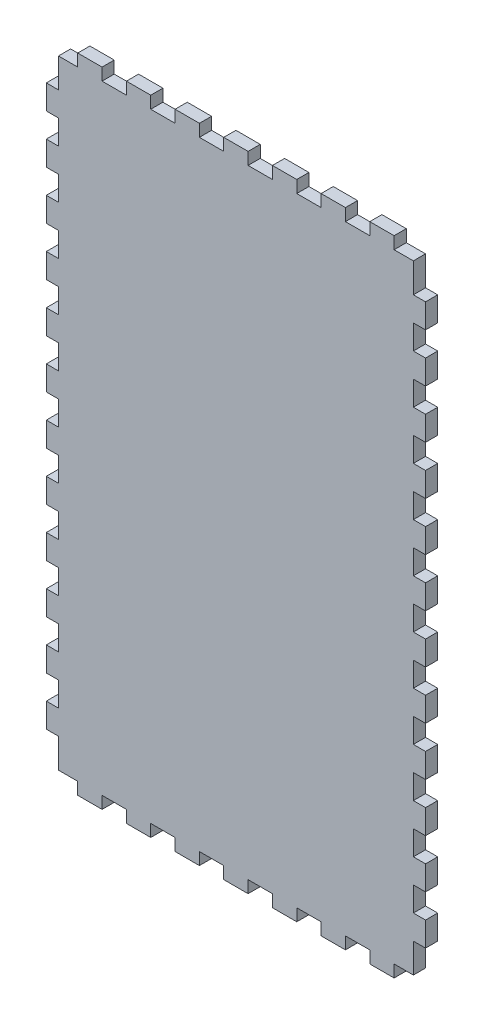
SolidWorks part; units mm, degrees
ref_plane "Front Plane" through (0, 0, 0) normal (0, 0, 1) x (1, 0, 0)
ref_plane "Top Plane" through (0, 0, 0) normal (0, 1, 0) x (1, 0, 0)
ref_plane "Right Plane" through (0, 0, 0) normal (1, 0, 0) x (0, 0, -1)
sketch "Sketch1" plane through (0, 0, 0) normal (0, 0, 1) x (1, 0, 0)
  line L0 (78, 0) -> (78, -6)
  line L1 (78, -6) -> (66, -6)
  line L2 (66, -6) -> (66, 0)
  line L3 (66, 0) -> (54, 0)
  line L4 (54, 0) -> (54, -6)
  line L5 (54, -6) -> (42, -6)
  line L6 (42, -6) -> (42, 0)
  line L7 (42, 0) -> (30, 0)
  line L8 (30, 0) -> (30, -6)
  line L9 (30, -6) -> (18, -6)
  line L10 (18, -6) -> (18, 0)
  line L11 (18, 0) -> (6, 0)
  line L12 (6, 0) -> (6, -6)
  line L13 (6, -6) -> (-6, -6)
  line L14 (-6, -6) -> (-6, 0)
  line L15 (-6, 0) -> (-18, 0)
  line L16 (-18, 0) -> (-18, -6)
  line L17 (-18, -6) -> (-30, -6)
  line L18 (-30, -6) -> (-30, 0)
  line L19 (-30, 0) -> (-42, 0)
  line L20 (-42, 0) -> (-42, -6)
  line L21 (-42, -6) -> (-54, -6)
  line L22 (-54, -6) -> (-54, 0)
  line L23 (-54, 0) -> (-66, 0)
  line L24 (-66, 0) -> (-66, -6)
  line L25 (-66, -6) -> (-78, -6)
  line L26 (-78, -6) -> (-78, 0)
  line L27 (-78, 0) -> (-87.5, 0)
  line L28 (-87.5, 0) -> (-87.5, 14.5)
  line L29 (-87.5, 14.5) -> (-93.5, 14.5)
  line L30 (-93.5, 14.5) -> (-93.5, 26.5)
  line L31 (-93.5, 26.5) -> (-87.5, 26.5)
  line L32 (-87.5, 26.5) -> (-87.5, 38.5)
  line L33 (-87.5, 38.5) -> (-93.5, 38.5)
  line L34 (-93.5, 38.5) -> (-93.5, 50.5)
  line L35 (-93.5, 38.5) -> (-93.5, 50.5) construction
  line L36 (-93.5, 50.5) -> (-87.5, 50.5)
  line L37 (-87.5, 62.5) -> (-93.5, 62.5)
  line L38 (-93.5, 62.5) -> (-93.5, 74.5)
  line L39 (-93.5, 74.5) -> (-87.5, 74.5)
  line L40 (-87.5, 74.5) -> (-87.5, 86.5)
  line L41 (-87.5, 86.5) -> (-93.5, 86.5)
  line L42 (-93.5, 86.5) -> (-93.5, 98.5)
  line L43 (-93.5, 98.5) -> (-87.5, 98.5)
  line L44 (-87.5, 98.5) -> (-87.5, 110.5)
  line L45 (-87.5, 110.5) -> (-93.5, 110.5)
  line L46 (-93.5, 110.5) -> (-93.5, 122.5)
  line L47 (-93.5, 122.5) -> (-87.5, 122.5)
  line L48 (-87.5, 122.5) -> (-87.5, 134.5)
  line L49 (-87.5, 134.5) -> (-93.5, 134.5)
  line L50 (-93.5, 134.5) -> (-93.5, 146.5)
  line L51 (-93.5, 146.5) -> (-87.5, 146.5)
  line L52 (-87.5, 146.5) -> (-87.5, 158.5)
  line L53 (-87.5, 158.5) -> (-93.5, 158.5)
  line L54 (-93.5, 158.5) -> (-93.5, 170.5)
  line L55 (-93.5, 170.5) -> (-87.5, 170.5)
  line L56 (-87.5, 158.5) -> (-87.5, 170.5) construction
  line L57 (-87.5, 170.5) -> (-87.5, 182.5)
  line L58 (-93.5, 182.5) -> (-87.5, 182.5) construction
  line L59 (-87.5, 182.5) -> (-93.5, 182.5)
  line L60 (-93.5, 182.5) -> (-93.5, 194.5)
  line L61 (-93.5, 194.5) -> (-87.5, 194.5)
  line L62 (-87.5, 194.5) -> (-87.5, 206.5)
  line L63 (-87.5, 206.5) -> (-93.5, 206.5)
  line L64 (-93.5, 206.5) -> (-93.5, 218.5)
  line L65 (-93.5, 218.5) -> (-87.5, 218.5)
  line L66 (-87.5, 218.5) -> (-87.5, 230.5)
  line L67 (-87.5, 230.5) -> (-93.5, 230.5)
  line L68 (-93.5, 230.5) -> (-93.5, 242.5)
  line L69 (-93.5, 242.5) -> (-87.5, 242.5)
  line L70 (-87.5, 242.5) -> (-87.5, 254.5)
  line L71 (-87.5, 254.5) -> (-87.5, 266.5) construction
  line L72 (-87.5, 254.5) -> (-93.5, 254.5)
  line L73 (-93.5, 254.5) -> (-87.5, 254.5) construction
  line L74 (-93.5, 254.5) -> (-93.5, 266.5)
  line L75 (-93.5, 266.5) -> (-87.5, 266.5)
  line L76 (-87.5, 266.5) -> (-87.5, 278.5)
  line L77 (-87.5, 278.5) -> (-93.5, 278.5)
  line L78 (-93.5, 278.5) -> (-93.5, 290.5)
  line L79 (-93.5, 290.5) -> (-87.5, 290.5)
  line L80 (-87.5, 290.5) -> (-87.5, 305)
  line L81 (-87.5, 305) -> (-78, 305)
  line L85 (-87.5, 50.5) -> (-87.5, 62.5)
  line L89 (87.5, 50.5) -> (87.5, 62.5)
  line L90 (87.5, 305) -> (78, 305)
  line L91 (87.5, 290.5) -> (87.5, 305)
  line L92 (93.5, 290.5) -> (87.5, 290.5)
  line L93 (93.5, 278.5) -> (93.5, 290.5)
  line L94 (87.5, 278.5) -> (93.5, 278.5)
  line L95 (87.5, 266.5) -> (87.5, 278.5)
  line L96 (93.5, 266.5) -> (87.5, 266.5)
  line L97 (93.5, 254.5) -> (93.5, 266.5)
  line L98 (87.5, 254.5) -> (93.5, 254.5)
  line L99 (87.5, 242.5) -> (87.5, 254.5)
  line L100 (93.5, 242.5) -> (87.5, 242.5)
  line L101 (93.5, 230.5) -> (93.5, 242.5)
  line L102 (87.5, 230.5) -> (93.5, 230.5)
  line L103 (87.5, 218.5) -> (87.5, 230.5)
  line L104 (93.5, 218.5) -> (87.5, 218.5)
  line L105 (93.5, 206.5) -> (93.5, 218.5)
  line L106 (87.5, 206.5) -> (93.5, 206.5)
  line L107 (87.5, 194.5) -> (87.5, 206.5)
  line L108 (93.5, 194.5) -> (87.5, 194.5)
  line L109 (93.5, 182.5) -> (93.5, 194.5)
  line L110 (87.5, 182.5) -> (93.5, 182.5)
  line L111 (87.5, 170.5) -> (87.5, 182.5)
  line L112 (93.5, 170.5) -> (87.5, 170.5)
  line L113 (93.5, 158.5) -> (93.5, 170.5)
  line L114 (87.5, 158.5) -> (93.5, 158.5)
  line L115 (87.5, 146.5) -> (87.5, 158.5)
  line L116 (93.5, 146.5) -> (87.5, 146.5)
  line L117 (93.5, 134.5) -> (93.5, 146.5)
  line L118 (87.5, 134.5) -> (93.5, 134.5)
  line L119 (87.5, 122.5) -> (87.5, 134.5)
  line L120 (93.5, 122.5) -> (87.5, 122.5)
  line L121 (93.5, 110.5) -> (93.5, 122.5)
  line L122 (87.5, 110.5) -> (93.5, 110.5)
  line L123 (87.5, 98.5) -> (87.5, 110.5)
  line L124 (93.5, 98.5) -> (87.5, 98.5)
  line L125 (93.5, 86.5) -> (93.5, 98.5)
  line L126 (87.5, 86.5) -> (93.5, 86.5)
  line L127 (87.5, 74.5) -> (87.5, 86.5)
  line L128 (93.5, 74.5) -> (87.5, 74.5)
  line L129 (93.5, 62.5) -> (93.5, 74.5)
  line L130 (87.5, 62.5) -> (93.5, 62.5)
  line L131 (93.5, 50.5) -> (87.5, 50.5)
  line L132 (93.5, 38.5) -> (93.5, 50.5)
  line L133 (87.5, 38.5) -> (93.5, 38.5)
  line L134 (87.5, 26.5) -> (87.5, 38.5)
  line L135 (93.5, 26.5) -> (87.5, 26.5)
  line L136 (93.5, 14.5) -> (93.5, 26.5)
  line L137 (87.5, 14.5) -> (93.5, 14.5)
  line L138 (87.5, 0) -> (87.5, 14.5)
  line L139 (78, 0) -> (87.5, 0)
  line L140 (-78, 311) -> (-78, 305)
  line L141 (-66, 311) -> (-78, 311)
  line L142 (-66, 305) -> (-66, 311)
  line L143 (-54, 305) -> (-66, 305)
  line L144 (-54, 311) -> (-54, 305)
  line L145 (-42, 311) -> (-54, 311)
  line L146 (-42, 305) -> (-42, 311)
  line L147 (-30, 305) -> (-42, 305)
  line L148 (-30, 311) -> (-30, 305)
  line L149 (-18, 311) -> (-30, 311)
  line L150 (-18, 305) -> (-18, 311)
  line L151 (-6, 305) -> (-18, 305)
  line L152 (-6, 311) -> (-6, 305)
  line L153 (6, 311) -> (-6, 311)
  line L154 (6, 305) -> (6, 311)
  line L155 (18, 305) -> (6, 305)
  line L156 (18, 311) -> (18, 305)
  line L157 (30, 311) -> (18, 311)
  line L158 (30, 305) -> (30, 311)
  line L159 (42, 305) -> (30, 305)
  line L160 (42, 311) -> (42, 305)
  line L161 (54, 311) -> (42, 311)
  line L162 (54, 305) -> (54, 311)
  line L163 (66, 305) -> (54, 305)
  line L164 (66, 311) -> (66, 305)
  line L165 (78, 311) -> (66, 311)
  line L166 (78, 305) -> (78, 311)
  point P156 (0, 152.5)
extrude "Boss-Extrude1" add sketch "Sketch1" along normal blind 6 contours L140 L81 L80 L79 L78 L77 L76 L75 L74 L72 L70 L69 L68 L67 L66 L65 L64 L63 L62 L61 L60 L59 L57 L55 L54 L53 L52 L51 L50 L49 L48 L47 L46 L45 L44 L43 L42 L41 L40 L39 L38 L37 L85 L36 L34 L33 L32 L31 L30 L29 L28 L27 L26 L25 L24 L23 L22 L21 L20 L19 L18 L17 L16 L15 L14 L13 L12 L11 L10 L9 L8 L7 L6 L5 L4 L3 L2 L1 L0 L139 L138 L137 L136 L135 L134 L133 L132 L131 L89 L130 L129 L128 L127 L126 L125 L124 L123 L122 L121 L120 L119 L118 L117 L116 L115 L114 L113 L112 L111 L110 L109 L108 L107 L106 L105 L104 L103 L102 L101 L100 L99 L98 L97 L96 L95 L94 L93 L92 L91 L90 L166 L165 L164 L163 L162 L161 L160 L159 L158 L157 L156 L155 L154 L153 L152 L151 L150 L149 L148 L147 L146 L145 L144 L143 L142 L141
